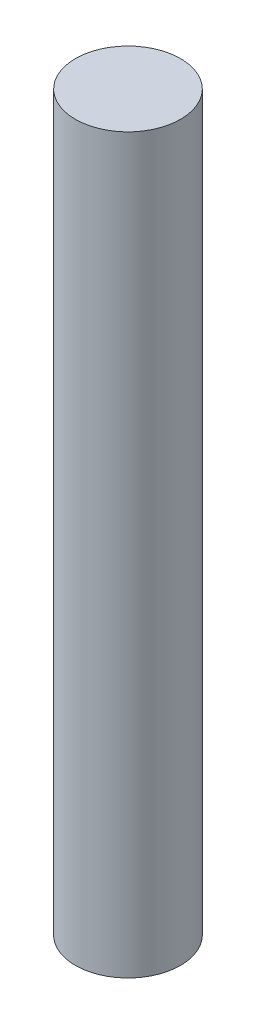
SolidWorks part; units mm, degrees
ref_plane "Front Plane" through (0, 0, 0) normal (0, 0, 1) x (1, 0, 0)
ref_plane "Top Plane" through (0, 0, 0) normal (0, 1, 0) x (1, 0, 0)
ref_plane "Right Plane" through (0, 0, 0) normal (1, 0, 0) x (0, 0, -1)
sketch "Sketch1" plane through (0, 0, 0) normal (0, 1, 0) x (1, 0, 0)
  circle A0 centre (0, 0) radius 38.1
  dimension "D1" = 76.2
extrude "Boss-Extrude1" add sketch "Sketch1" along normal blind 530.86
equation "\"Motor_Length\"= 20.90in"
equation "\"Motor_OD\"= 3in"
equation "\"D1@Sketch1\"=\"Motor_OD\""
equation "\"D1@Boss-Extrude1\"=\"Motor_Length\""
